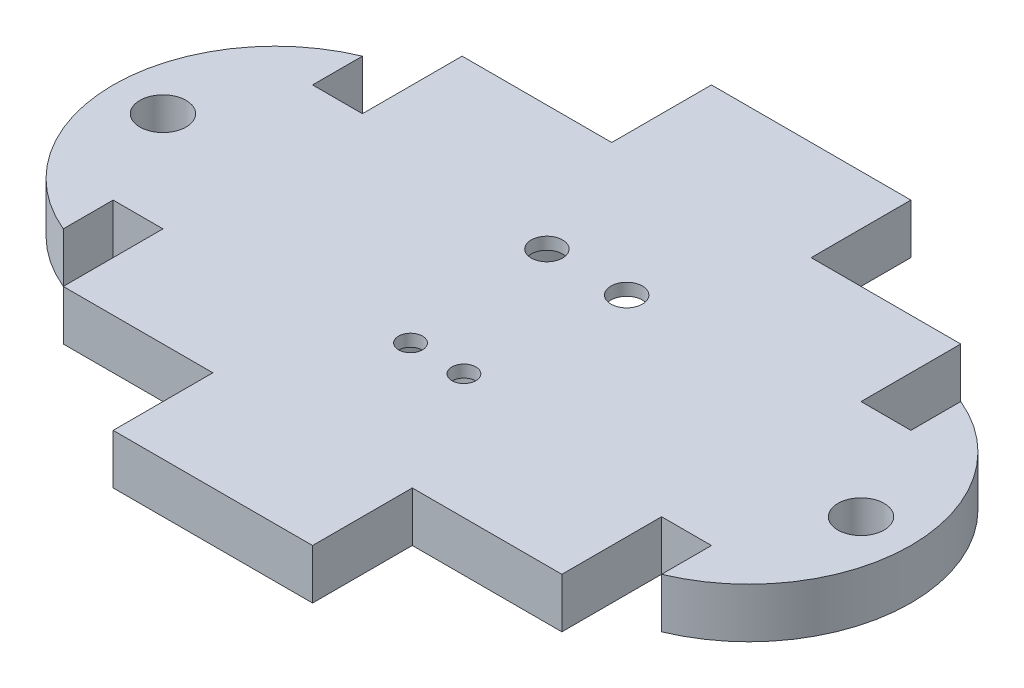
SolidWorks part; units mm, degrees
material "Acrylic (Medium-high impact)"
ref_plane "Front Plane" through (0, 0, 0) normal (0, 0, 1) x (1, 0, 0)
ref_plane "Top Plane" through (0, 0, 0) normal (0, 1, 0) x (1, 0, 0)
ref_plane "Right Plane" through (0, 0, 0) normal (1, 0, 0) x (0, 0, -1)
sketch "Sketch1" plane through (0, 0, 0) normal (0, 1, 0) x (1, 0, 0)
  line L0 (0, 2.5414) -> (0, -2.9418) construction
  line L1 (-15.875, 12.7) -> (-6.35, 12.7)
  line L2 (-15.875, 12.7) -> (-15.875, 6.35)
  line L3 (-15.875, -12.7) -> (-6.35, -12.7)
  line L4 (15.875, 12.7) -> (15.875, 6.35)
  line L5 (-15.875, 12.7) -> (15.875, -12.7) construction
  line L6 (-15.875, -12.7) -> (15.875, 12.7) construction
  line L7 (-15.875, 6.35) -> (-19.05, 6.35)
  line L8 (-19.05, 6.35) -> (-19.05, -6.35) construction
  line L9 (-15.875, -6.35) -> (-19.05, -6.35)
  line L10 (15.875, -6.35) -> (19.05, -6.35)
  line L11 (15.875, 6.35) -> (19.05, 6.35)
  line L12 (6.35, 12.7) -> (15.875, 12.7)
  line L13 (-15.875, -6.35) -> (-15.875, -12.7)
  line L14 (-35.8829, 0) -> (4.5103, 0) construction
  line L15 (15.875, -6.35) -> (15.875, -12.7)
  line L16 (-6.35, 12.7) -> (-6.35, 19.05)
  line L17 (-6.35, 19.05) -> (6.35, 19.05)
  line L18 (6.35, 12.7) -> (6.35, 19.05)
  line L19 (6.35, -12.7) -> (6.35, -19.05)
  line L20 (-6.35, -19.05) -> (6.35, -19.05)
  line L21 (-6.35, -12.7) -> (-6.35, -19.05)
  line L22 (6.35, -12.7) -> (15.875, -12.7)
  line L23 (-19.05, 6.35) -> (-19.05, 9.525)
  line L28 (-19.05, -6.35) -> (-19.05, -9.525)
  line L29 (19.05, -6.35) -> (19.05, -9.525)
  line L32 (19.05, 6.35) -> (19.05, 9.525)
  arc A0 (-22.225, 5.4993) -> (-22.225, -5.4993) centre (-19.05, 0) ccw construction
  circle A1 centre (-22.225, 0) radius 3.175 construction
  arc A3 (-19.05, 9.525) -> (-19.05, -9.525) centre (-15.0812, 0) ccw
  arc A4 (19.05, 9.525) -> (19.05, -9.525) centre (15.0812, 0) cw
  point P0 (0, 0)
  point P24 (0, 19.05)
  dimension "D3" = 6.35
  dimension "D1" = 25.4
  dimension "D2" = 31.75
  dimension "D4" = 3.175
  dimension "D5" = 12.7
  dimension "D6" = 12.7
  dimension "D7" = 6.35
  dimension "D8" = 19.05
extrude "Boss-Extrude1" add sketch "Sketch1" along normal blind 3.175
hole_wizard "#4 Clearance Hole1" positions "Sketch3" profile "Sketch2" hole size "#4" standard "Ansi Inch"
sketch "Sketch3" plane through (0, 3.175, 0) normal (0, 1, 0) x (-1, 0, 0)
  line L2 (22.225, 0) -> (-22.225, 0) construction
  circle A3 centre (22.225, 0) radius 3.175 construction
  point P0 (-22.225, 0)
  point P1 (22.225, 0)
sketch "Sketch2" plane through (22.225, 3.175, 0) normal (1, 0, 0) x (0, 0, 1)
  line L0 (0, 0) -> (0, 7.2352)
  line L1 (0, 7.2352) -> (1.4732, 6.35)
  line L2 (1.4732, 6.35) -> (1.4732, 0)
  line L5 (1.4732, 0) -> (0, 0)
  line L10 (0, 7.2352) -> (-1.4732, 6.35) construction
  line L11 (0, -6.35) -> (0, 107.95) construction
  dimension "Hole Dia." = 2.9464
  dimension "Hole Depth" = 6.35
  dimension "Drill Angle" = 118
sketch "Sketch4" plane through (0, 0, 0) normal (0, 1, 0) x (1, 0, 0)
  line L0 (-1.7, -4.7625) -> (1.7, -4.7625) construction
  line L1 (0, 0) -> (0, 4.7625) construction
  line L2 (0, 0) -> (0, -4.7625) construction
  line L3 (-2.54, 4.7625) -> (2.54, 4.7625) construction
  circle A0 centre (0, 4.7625) radius 5.08
  circle A1 centre (-1.7, -4.7625) radius 0.762
  circle A2 centre (1.7, -4.7625) radius 0.762
  circle A3 centre (0, -4.7625) radius 2.6035
  circle A4 centre (-2.54, 4.7625) radius 1
  circle A5 centre (2.54, 4.7625) radius 1
  point P6 (0, -4.7625)
  dimension "D1" = 10.16
  dimension "D2" = 1.524
  dimension "D4" = 5.207
  dimension "D5" = 9.525
  dimension "D6" = 2
  dimension "D3" = 3.4
  dimension "D7" = 5.08
extrude "Cut-Extrude3" cut sketch "Sketch4" along normal up to next contours A1 | A2 | A5 | A4 region at (-1.7, 0, 4.7625) region at (1.7, 0, 4.7625) region at (2.54, 0, -4.7625)
extrude "Cut-Extrude4" cut sketch "Sketch4<3>" along normal blind 2.4 contours A3 A1 A2 | A2 | A0 A5 A4 | A2 region at (0, 0, -4.7625) region at (1.7, 0, 4.7625) region at (0, 0, 4.7625)
sketch "Sketch4<3>" plane through (0, 0, 0) normal (0, 1, 0) x (1, 0, 0) same geometry as "Sketch4"
sketch "Sketch5" [suppressed] plane through (0, 3.175, 0) normal (0, 1, 0) x (1, 0, 0)
  point P0 (-19.05, 6.35)
  point P1 (-15.875, 6.35)
  point P3 (-19.05, -6.35)
  point P5 (-15.875, -6.35)
  point P7 (-6.35, 12.7)
  point P9 (6.35, 12.7)
  point P11 (15.875, 6.35)
  point P13 (19.05, 6.35)
  point P15 (19.05, -6.35)
  point P17 (15.875, -6.35)
  point P19 (6.35, -12.7)
  point P21 (-6.35, -12.7)
sketch "Sketch6" [suppressed] plane through (0, 3.175, 0) normal (0, 1, 0) x (1, 0, 0)
  circle A0 centre (-19.05, 6.35) radius 0.635
  dimension "D1" = 1.27
extrude "Cut-Extrude6" [suppressed] cut sketch "Sketch6" against normal up to next
pattern_sketch "Sketch-Pattern1" [suppressed] of bodies 106 driven by "Sketch5"
